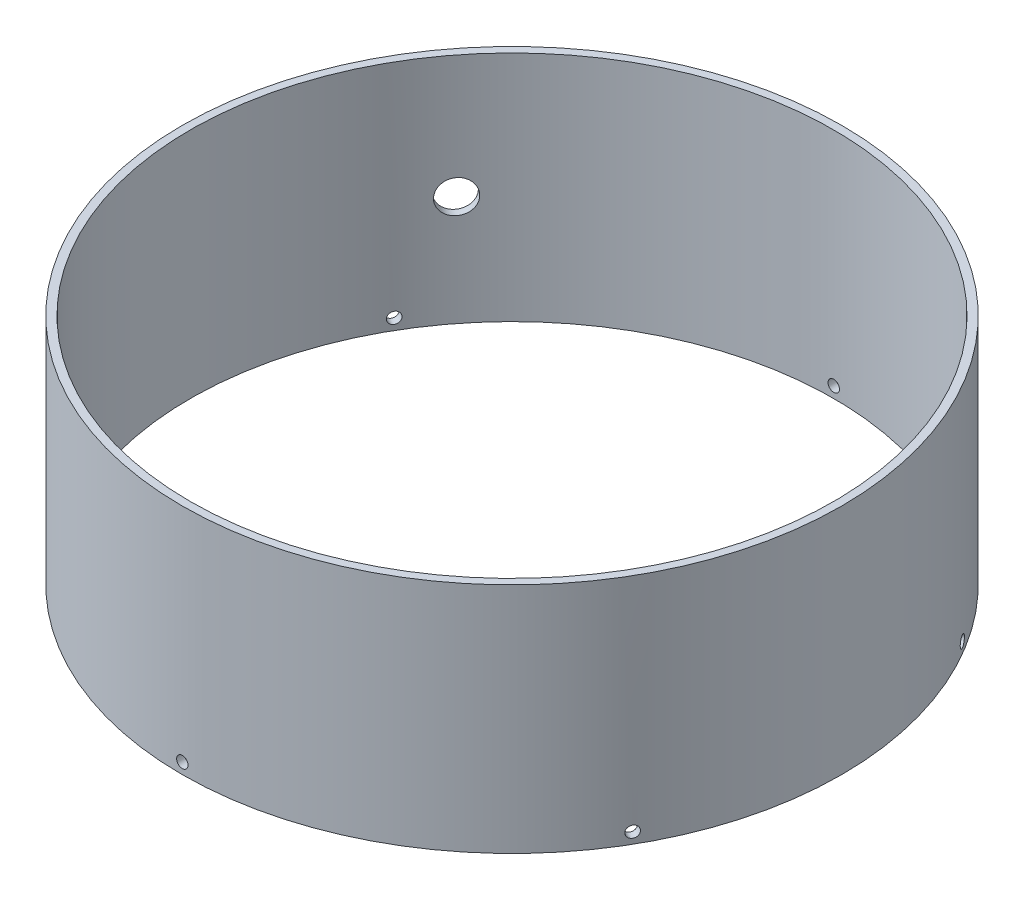
SolidWorks part; units mm, degrees
ref_plane "Front Plane" through (0, 0, 0) normal (0, 0, 1) x (1, 0, 0)
ref_plane "Top Plane" through (0, 0, 0) normal (0, 1, 0) x (1, 0, 0)
ref_plane "Right Plane" through (0, 0, 0) normal (1, 0, 0) x (0, 0, -1)
sketch "Sketch2" plane through (0, 0, 0) normal (0, 1, 0) x (1, 0, 0)
  circle A0 centre (0, 0) radius 76.2
  circle A1 centre (0, 0) radius 74.3712
  dimension "D1" = 152.4
  dimension "D2" = 1.8288
extrude "Boss-Extrude1" add sketch "Sketch2" along normal blind 53.7718 contours A0 A1 region at (-75.9845, 0, 0)
sketch "Sketch3" plane through (0, 0, 0) normal (0, 0, 1) x (1, 0, 0)
  circle A0 centre (0, 2.54) radius 1.3208
  dimension "D1" = 2.6416
  dimension "D2" = 2.54
extrude "Cut-Extrude1" cut sketch "Sketch3" along normal up to surface (76.1886 mm away) contours A0 region at (0, 2.54, 0) up to face at (0, 53.7718, 76.2)
pattern_circular "CirPattern1" count 6 over 360 about axis through (0, 53.7718, 0) along (0, -1, 0) of "Cut-Extrude1"
sketch "Sketch4" plane through (0, 0, 0) normal (0, 1, 0) x (1, 0, 0)
  line L0 (0, 0) -> (27.9466, 0) construction
  line L1 (0, 0) -> (-34.5326, 26.9798) construction
  dimension "D1" = 142
ref_plane "Plane1" through (0, 0, 0) normal (-0.788, 0, -0.6157) x (-0.6157, 0, 0.788)
sketch "Sketch5" plane through (0, 0, 0) normal (-0.788, 0, -0.6157) x (-0.6157, 0, 0.788)
  circle A0 centre (0, 25.4) radius 3.81
  dimension "D1" = 7.62
  dimension "D2" = 25.4
extrude "Cut-Extrude2" cut sketch "Sketch5" along normal through all contours A0 region at (0, 25.4, 0)
equation "\"Middle Coupler Inner Daimeter\"= 3.875in"
equation "\"Middle Coupler  Wall Thickness\" = 0.25in"
equation "\"Middle Coupler Bottom Thickness\"= 0.2in"
equation "\"Bearing Rail Offset\"= 0.45in"
equation "\"3-56 UNF Tap\"= 0.089in"
equation "\"3-48 Tap\"= 0.079in"
equation "\"3-56 UNF Clearance\"= 0.104in"
equation "\"3-48 Clearance\" = 0.104in"
equation "\"Ball Bearing Distance\"= 0.03in"
equation "\"TCA Outer Diameter\" = 6in"
equation "\"Interstage Aeroframe Wall Thickness\" = 0.072in"
equation "\"Compression Spring OD\"= 0.42in"
equation "\"10-24 Tap\"= 0.157in"
equation "\"10-24 Clearance\"= 0.196in"
equation "\"Lower Stage Fuselage Wall Thickness\" = 0.25in"
equation "\"6-32 Tap\" = 0.107in"
equation "\"6-32 Clearance\" = 0.144"
equation "\"1/4-20 Tap\" = 0.201in"
equation "\"12-24 Tap\" = 0.177in"
equation "\"D1@Sketch2\"=\"TCA Outer Diameter\""
equation "\"D1@Sketch3\"=\"3-48 Clearance\""
equation "\"D1@Boss-Extrude1\"=2.167000in - 0.05"
